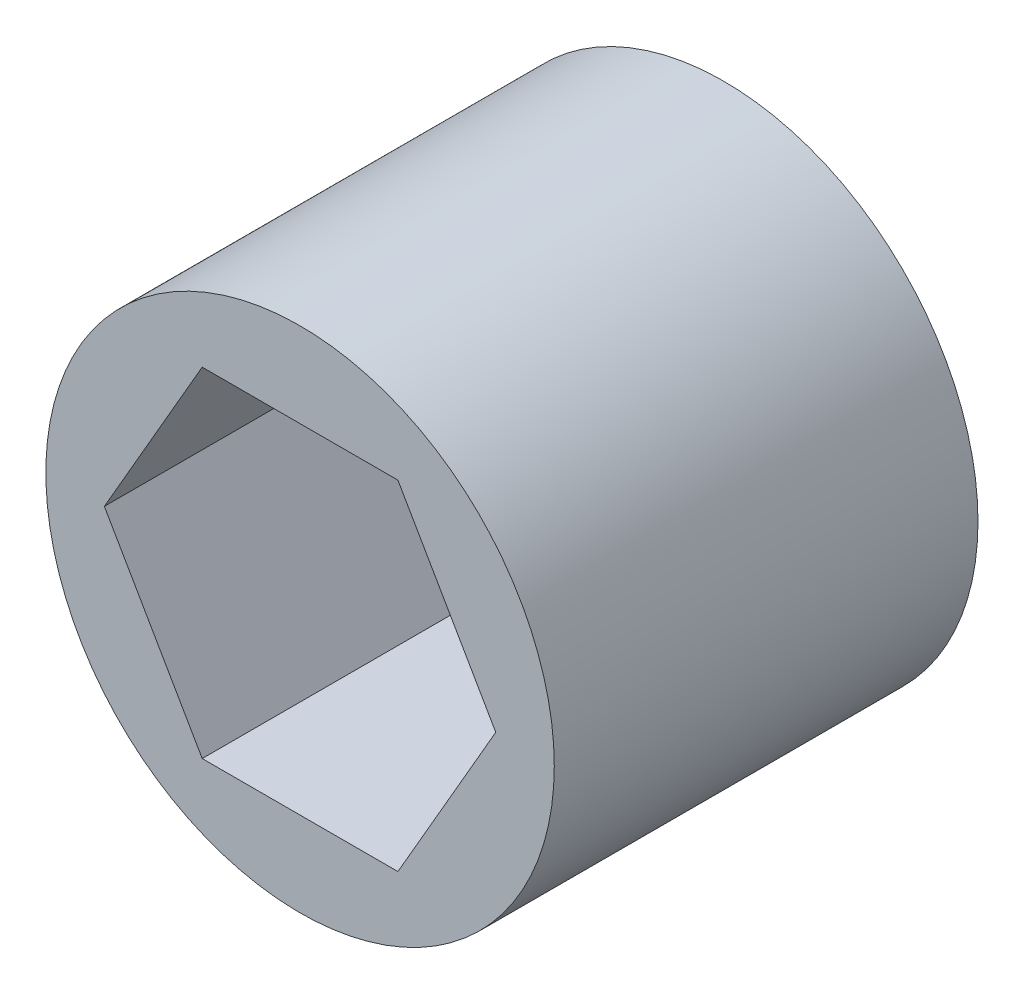
SolidWorks part; units mm, degrees
material "Nylon 101"
ref_plane "Front Plane" through (0, 0, 0) normal (0, 0, 1) x (1, 0, 0)
ref_plane "Top Plane" through (0, 0, 0) normal (0, 1, 0) x (1, 0, 0)
ref_plane "Right Plane" through (0, 0, 0) normal (1, 0, 0) x (0, 0, -1)
sketch "Sketch1" plane through (0, 0, 0) normal (0, 0, 1) x (1, 0, 0)
  line L1 (-3.6662, 6.35) -> (-7.3323, 0)
  line L2 (-7.3323, 0) -> (-3.6662, -6.35)
  line L3 (-3.6662, -6.35) -> (3.6662, -6.35)
  line L4 (3.6662, -6.35) -> (7.3323, 0)
  line L5 (7.3323, 0) -> (3.6662, 6.35)
  line L6 (3.6662, 6.35) -> (-3.6662, 6.35)
  circle A0 centre (0, 0) radius 6.35 construction
  circle A1 centre (0, 0) radius 9.525
  point P10 (0, 6.35)
  dimension "D1" = 12.7
  dimension "D2" = 19.05
extrude "Boss-Extrude1" add sketch "Sketch1" along normal blind 15.875
